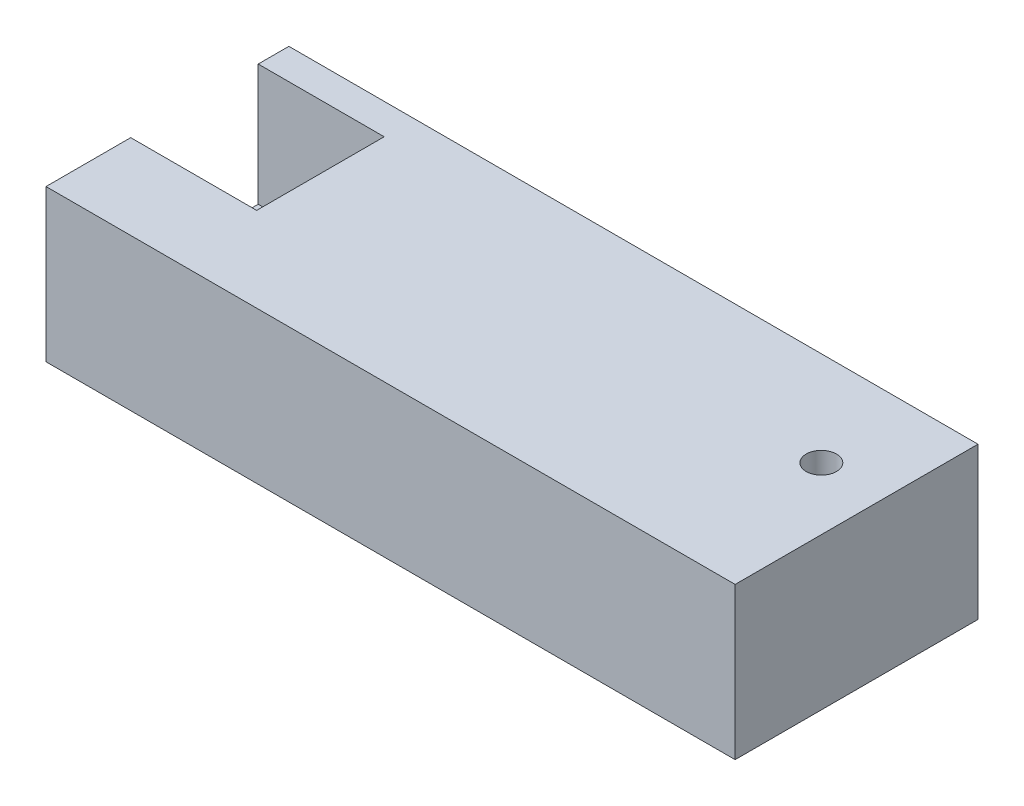
SolidWorks part; units mm, degrees
material "ABS"
ref_plane "Front Plane" through (0, 0, 0) normal (0, 0, 1) x (1, 0, 0)
ref_plane "Top Plane" through (0, 0, 0) normal (0, 1, 0) x (1, 0, 0)
ref_plane "Right Plane" through (0, 0, 0) normal (1, 0, 0) x (0, 0, -1)
sketch "Sketch1" plane through (0, 0, 0) normal (0, 1, 0) x (1, 0, 0)
  line L1 (-113.5, -40) -> (113.5, -40)
  line L2 (-113.5, -40) -> (-113.5, 40)
  line L3 (-113.5, 40) -> (113.5, 40)
  line L4 (113.5, -40) -> (113.5, 40)
  line L5 (-113.5, -40) -> (113.5, 40) construction
  line L6 (-113.5, 40) -> (113.5, -40) construction
  circle A0 centre (-93, 8.9) radius 5
  circle A1 centre (93, 8.9) radius 5
  point P0 (0, 0)
  dimension "D6" = 10
  dimension "D7" = 10
  dimension "D1" = 227
  dimension "D2" = 186
  dimension "D4" = 48.9
  dimension "D5" = 80
  dimension "D3" = 93
extrude "Boss-Extrude1" add sketch "Sketch1" along normal blind 50
sketch "Sketch2" plane through (0, 50, 0) normal (0, 1, 0) x (1, 0, 0)
  line L1 (-114, -12.1) -> (-72, -12.1)
  line L2 (-114, -12.1) -> (-114, 29.9)
  line L3 (-114, 29.9) -> (-72, 29.9)
  line L4 (-72, -12.1) -> (-72, 29.9)
  line L5 (-114, -12.1) -> (-72, 29.9) construction
  line L6 (-114, 29.9) -> (-72, -12.1) construction
  point P0 (-93, 8.9)
  dimension "D1" = 42
extrude "Cut-Extrude1" cut sketch "Sketch2" against normal blind 40
equation "\"D3@Sketch1\"=\"D2@Sketch1\"/2"
